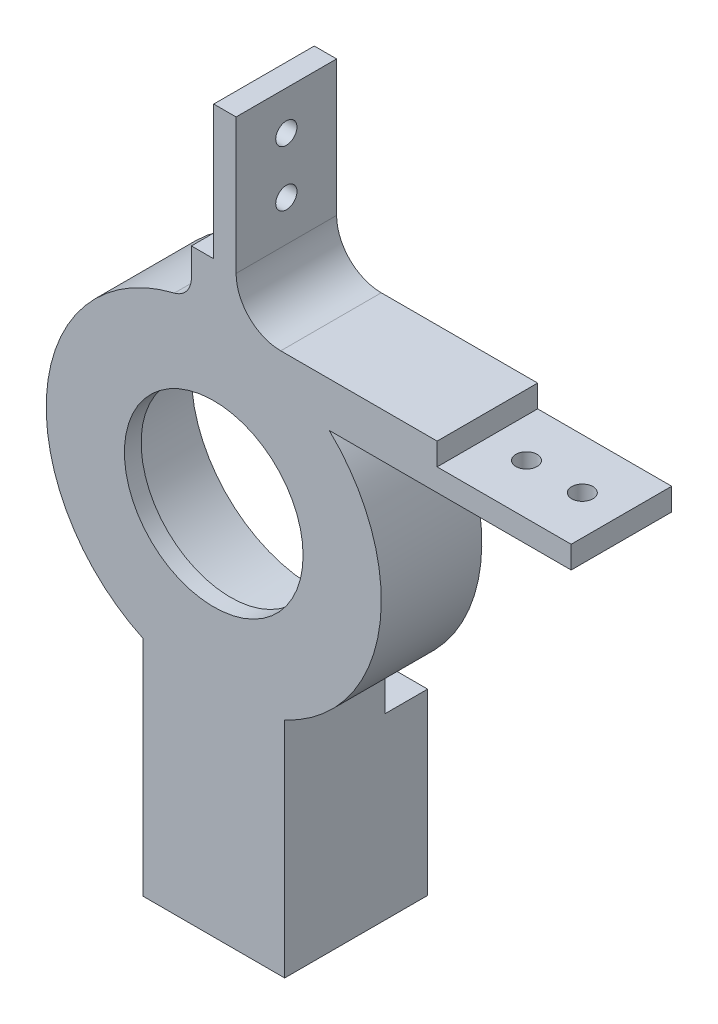
SolidWorks part; units mm, degrees
note: '?' marks a value the reader was unsure of.
ref_plane "Front Plane" through (0, 0, 0) normal (0, 0, 1) x (1, 0, 0)
ref_plane "Top Plane" through (0, 0, 0) normal (0, 1, 0) x (1, 0, 0)
ref_plane "Right Plane" through (0, 0, 0) normal (1, 0, 0) x (0, 0, -1)
ref_axis "X-Axis" through (-88.99, 0, 0) along (1, 0, 0)?
ref_axis "Y-Axis" through (0, 55, 0) along (0, -1, 0)?
ref_axis "Z-Axis" through (0, 0, -88.99) along (0, 0, 1)?
sketch "Sketch2" plane through (0, 0, 0) normal (0, 0, 1) x (1, 0, 0)
  circle A0 centre (0, 0) radius 11
  circle A1 centre (0, 0) radius 15
  dimension "D1" = 22
  dimension "D2" = 30
extrude "Boss-Extrude1" add sketch "Sketch2" along normal blind 9
sketch "Sketch3" plane through (0, 0, 0) normal (0, 0, 1) x (1, 0, 0)
  line L0 (-6.35, -13.5896) -> (-6.35, 0) construction
  line L1 (-10.8585, 57.4383) -> (10.8585, 57.4383) construction
  line L2 (-6.35, -13.5896) -> (-6.35, -33.5896)
  line L3 (-6.35, -33.5896) -> (6.35, -33.5896)
  line L4 (6.35, -13.5896) -> (6.35, -33.5896)
  line L5 (-10.8585, 57.4383) -> (6.35, -33.5896) construction
  line L6 (-6.35, -33.5896) -> (10.8585, 57.4383) construction
  line L7 (-6.35, 0) -> (0, 0) construction
  line L8 (6.35, 0) -> (6.35, -13.5896) construction
  line L9 (6.35, 0) -> (0, 0) construction
  circle A2 centre (0, 0) radius 15
  arc A3 (-6.35, -13.5896) -> (6.35, -13.5896) centre (0, 0) ccw
  point P0 (0, 0)
  dimension "D2" = 12.7
  dimension "D3" = 20
  dimension "D1" = 0
extrude "Boss-Extrude2" add sketch "Sketch3" along normal blind 9
sketch "Sketch4" plane through (0, 0, 0) normal (0, 0, 1) x (1, 0, 0)
  line L0 (6.35, -33.5896) -> (6.35, -13.5896) construction
  line L1 (-6.35, -33.5896) -> (6.35, -33.5896)
  line L2 (-6.35, -33.5896) -> (-6.35, -17.5896)
  line L3 (-6.35, -17.5896) -> (6.35, -17.5896)
  line L4 (6.35, -33.5896) -> (6.35, -17.5896)
  dimension "D1" = 16
extrude "Boss-Extrude3" add sketch "Sketch4" against normal offset from surface (3.8 mm away) 12.8 up to face at (0, -16.4422, 9)
sketch "Sketch5" plane through (0, -33.5896, 0) normal (0, -1, 0) x (1, 0, 0)
  line L0 (-6.35, 2.6) -> (6.35, 2.6) construction
  line L1 (-6.35, 9) -> (-6.35, -3.8) construction
  line L2 (6.35, 9) -> (6.35, -3.8) construction
  line L3 (6.35, 2.6) -> (0, 10) construction
  line L5 (0, 10) -> (0, -3.8) construction
  line L6 (6.35, -3.8) -> (-6.35, -3.8) construction
  circle A0 centre (0, 2.6) radius 1.275
  dimension "D1" = 2.55
extrude "Cut-Extrude1" cut sketch "Sketch5" against normal blind 7
sketch "Sketch6" plane through (0, 0, 9) normal (0, 0, 1) x (1, 0, 0)
  circle A1 centre (0, 0) radius 8
  circle A2 centre (0, 0) radius 11
  circle A3 centre (0, 0) radius 11
  dimension "D1" = 0
  dimension "D2" = 3
extrude "Boss-Extrude4" add sketch "Sketch6" against normal blind 1.5
sketch "Sketch7" plane through (0, 0, 0) normal (0, 0, 1) x (1, 0, 0)
  line L0 (-2, 14.8661) -> (2, 10.8661)
  line L1 (-2, 31) -> (2, 31)
  line L2 (-2, 31) -> (-2, 14.8661)
  line L3 (-4.2216, -18.7724) -> (4.2216, -18.7724) construction
  line L4 (2, 31) -> (2, 14.8661)
  line L5 (-2, 31) -> (4.2216, -18.7724) construction
  line L6 (-4.2216, -18.7724) -> (2, 31) construction
  line L11 (2, 14.8661) -> (32, 14.8661)
  line L12 (2, 14.8661) -> (2, 10.8661) construction
  line L13 (2, 10.8661) -> (32, 10.8661)
  line L14 (32, 14.8661) -> (32, 10.8661)
  arc A2 (6.35, -13.5896) -> (-6.35, -13.5896) centre (0, 0) ccw
  arc A3 (2, 14.8661) -> (-2, 14.8661) centre (0, 0) ccw construction
  point P0 (0, 15)
  dimension "D2" = 16
  dimension "D3" = 4
  dimension "D4" = 4
  dimension "D5" = 30
  dimension "D1" = 0
extrude "Boss-Extrude5" add sketch "Sketch7" along normal up to surface (9 mm away) up to face at (0, -16.4422, 9)
sketch "Sketch8" plane through (0, 0, 9) normal (0, 0, 1) x (1, 0, 0)
  line L1 (32, 14.8661) -> (20, 14.8661)
  line L2 (32, 14.8661) -> (32, 12.8661)
  line L3 (32, 12.8661) -> (20, 12.8661)
  line L4 (20, 14.8661) -> (20, 12.8661)
  line L5 (-2, 31) -> (0, 31)
  line L6 (-2, 31) -> (-2, 19)
  line L7 (-2, 19) -> (0, 19)
  line L8 (0, 31) -> (0, 19)
  dimension "D1" = 2
  dimension "D2" = 12
extrude "Cut-Extrude2" cut sketch "Sketch8" against normal through all
sketch "Sketch9" plane through (0, 0, 0) normal (-1, 0, 0) x (0, 0, 1)
  line L0 (4.5, 31) -> (4.5, 19) construction
  line L1 (0, 31) -> (9, 31) construction
  line L2 (0, 19) -> (9, 19) construction
  line L3 (0, 19) -> (9, 19) construction
  circle A0 centre (4.5, 27.5) radius 0.95
  circle A1 centre (4.5, 22.5) radius 0.95
  dimension "D1" = 1.9
  dimension "D2" = 3.5
  dimension "D3" = 3.5
extrude "Cut-Extrude3" cut sketch "Sketch9" against normal up to next
sketch "Sketch10" plane through (0, 12.8661, 0) normal (0, 1, 0) x (1, 0, 0)
  line L0 (20, -4.5) -> (32, -4.5) construction
  line L1 (20, -9) -> (20, 0) construction
  line L2 (32, 0) -> (32, -9) construction
  circle A0 centre (23.5, -4.5) radius 0.95
  circle A1 centre (28.5, -4.5) radius 0.95
  dimension "D1" = 1.9
  dimension "D2" = 3.5
  dimension "D3" = 3.5
extrude "Cut-Extrude4" cut sketch "Sketch10" against normal up to next
fillet "Fillet1" radius 4 1 edges at (2, 14.8661, 4.5)
fillet "Fillet3" radius 2 1 edges at (-2, 14.8661, 4.5)
sketch "Sketch11" plane through (0, 0, 0) normal (0, 0, -1) x (-1, 0, 0)
  line L13 (-10.3406, 10.8661) -> (-6, 14.8661)
  line L14 (2, 19) -> (-2, 19)
  line L15 (-2, 19) -> (-2, 18.8661)
  line L26 (-20, 14.8661) -> (-20, 12.8661)
  line L27 (-20, 12.8661) -> (-32, 12.8661)
  line L28 (-32, 12.8661) -> (-32, 10.8661)
  line L29 (-32, 10.8661) -> (-10.3406, 10.8661)
  line L30 (-6.35, -13.5896) -> (-6.35, -17.5896)
  line L31 (-6.35, -17.5896) -> (6.35, -17.5896)
  line L32 (6.35, -17.5896) -> (6.35, -13.5896)
  line L33 (2, 16.5227) -> (2, 19)
  line L34 (2, 19) -> (0, 19)
  line L35 (0, 19) -> (0, 31)
  line L36 (0, 31) -> (-2, 31)
  line L37 (-2, 31) -> (-2, 18.8661)
  line L38 (-6, 14.8661) -> (-20, 14.8661)
  line L39 (-20, 14.8661) -> (-20, 12.8661) construction
  line L40 (-20, 12.8661) -> (-32, 12.8661) construction
  line L41 (-32, 12.8661) -> (-32, 10.8661)
  line L42 (-32, 10.8661) -> (-10.3406, 10.8661) construction
  line L43 (-6.35, -13.5896) -> (-6.35, -17.5896)
  line L44 (-6.35, -17.5896) -> (6.35, -17.5896)
  line L45 (6.35, -17.5896) -> (6.35, -13.5896)
  line L46 (2, 16.5227) -> (2, 19)
  line L47 (2, 19) -> (0, 19) construction
  line L48 (0, 19) -> (0, 31) construction
  line L49 (0, 31) -> (-2, 31) construction
  line L50 (-2, 31) -> (-2, 18.8661) construction
  line L51 (-6, 14.8661) -> (-20, 14.8661) construction
  arc A3 (6.35, -13.5896) -> (3.5294, 14.5789) centre (0, 0) ccw
  arc A4 (-10.3406, 10.8661) -> (-6.35, -13.5896) centre (0, 0) ccw
  arc A6 (-10.3406, 10.8661) -> (-6.35, -13.5896) centre (0, 0) ccw
  arc A7 (6.35, -13.5896) -> (3.5294, 14.5789) centre (0, 0) ccw
  arc A8 (-6, 14.8661) -> (-2, 18.8661) centre (-6, 18.8661) ccw
  arc A9 (-10.3406, 10.8661) -> (-6.35, -13.5896) centre (0, 0) ccw
  arc A10 (6.35, -13.5896) -> (3.5294, 14.5789) centre (0, 0) ccw
  arc A11 (-6, 14.8661) -> (-2, 18.8661) centre (-6, 18.8661) ccw
  arc A12 (2, 16.5227) -> (3.5294, 14.5789) centre (4, 16.5227) ccw
  arc A13 (2, 16.5227) -> (3.5294, 14.5789) centre (4, 16.5227) ccw
  dimension "D1" = 0
extrude "Boss-Extrude6" add sketch "Sketch11" along normal blind 1.5 separate body
sketch "Sketch13" plane through (0, 0, -1.5) normal (0, 0, -1) x (-1, 0, 0)
  line L0 (0, 19) -> (0, -17.5896) construction
  line L1 (2, 19) -> (-2, 19) construction
  line L2 (-6.35, -17.5896) -> (6.35, -17.5896) construction
  circle A0 centre (0, 15) radius 0.95
  circle A1 centre (0, -15) radius 0.95
  dimension "D1" = 1.9
  dimension "D2" = 15
  dimension "D3" = 15
extrude "Cut-Extrude5" cut sketch "Sketch13" against normal blind 9
fillet "Fillet2" radius 1 2 edges at (0, 19, -1.5) (2, 18.933, -1.5)
delete or keep bodies "Body-Delete/Keep 1" [suppressed] type delete bodies bodies 111
delete or keep bodies "Body-Delete/Keep 2" type delete bodies bodies 112
sketch "Sketch14" [suppressed] plane through (0, 0, -1.5) normal (0, 0, -1) x (-1, 0, 0)
  circle A1 centre (0, 0) radius 8
  circle A2 centre (0, 0) radius 11
  circle A3 centre (0, 0) radius 11
  dimension "D1" = 0
  dimension "D2" = 3
extrude "Boss-Extrude7" [suppressed] add sketch "Sketch14" against normal up to surface (1.5 mm away)
